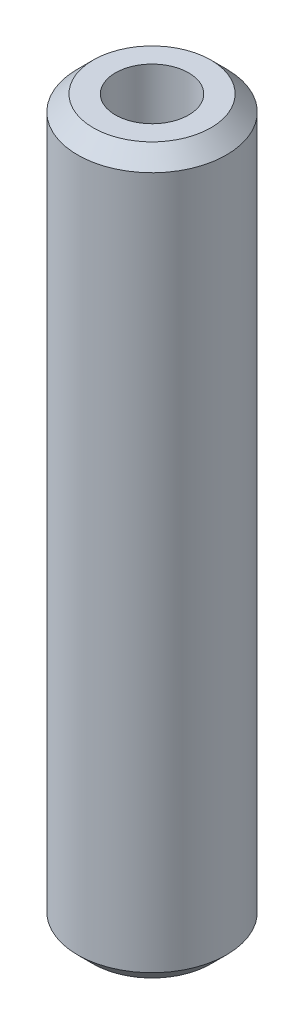
SolidWorks part; units mm, degrees
ref_plane "Front Plane" through (0, 0, 0) normal (0, 0, 1) x (1, 0, 0)
ref_plane "Top Plane" through (0, 0, 0) normal (0, 1, 0) x (1, 0, 0)
ref_plane "Right Plane" through (0, 0, 0) normal (1, 0, 0) x (0, 0, -1)
sketch "Sketch1" plane through (0, 0, 0) normal (0, 1, 0) x (1, 0, 0)
  circle A0 centre (0, 0) radius 25
  dimension "SHAFT_OD" = 50
extrude "Boss-Extrude1" add sketch "Sketch1" along normal blind 243.1621
sketch "Sketch2" plane through (0, 0, 0) normal (0, 1, 0) x (1, 0, 0)
  circle A0 centre (0, 0) radius 12.2879
  dimension "BORE_D" = 24.5758
extrude "Cut-Extrude1" cut sketch "Sketch2" along normal through all
chamfer "Chamfer1" distance 5.2602 angle 45 2 edges at (0, 243.1621, 25) (0, 0, 25)
